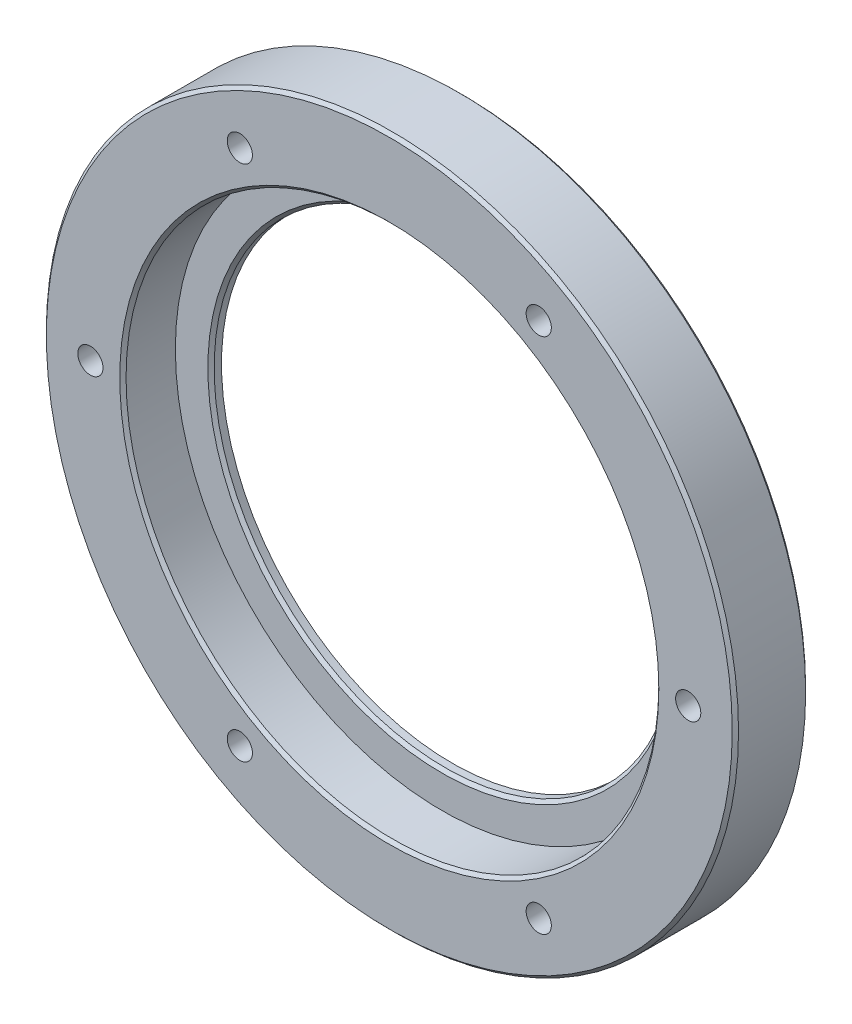
SolidWorks part; units mm, degrees
other "Markup1"
sketch "Sketch6" plane through (33, 33, 7.2446) normal (0.7002, 0.6134, 0.3652) x (0.5544, -0.7895, 0.2632)
material "6061-O (SS)"
ref_plane "Front Plane" through (0, 0, 0) normal (0, 0, 1) x (1, 0, 0)
ref_plane "Top Plane" through (0, 0, 0) normal (0, 1, 0) x (1, 0, 0)
ref_plane "Right Plane" through (0, 0, 0) normal (1, 0, 0) x (0, 0, -1)
sketch "Sketch1" plane through (0, 0, 0) normal (0, 0, 1) x (1, 0, 0)
  circle A0 centre (0, 0) radius 33
  dimension "D1" = 66
extrude "Main Body" add sketch "Sketch1" along normal blind 7
sketch "Sketch2" plane through (0, 0, 7) normal (0, 0, 1) x (1, 0, 0)
  circle A0 centre (0, 0) radius 22
  dimension "D1" = 44
extrude "Optical Cutout" cut sketch "Sketch2" against normal through all
sketch "Sketch3" plane through (0, 0, 7) normal (0, 0, 1) x (1, 0, 0)
  circle A0 centre (0, 0) radius 25.4
  dimension "D1" = 50.8
extrude "Window Cutout" cut sketch "Sketch3" against normal blind 5
sketch "Sketch4" plane through (0, 0, 0) normal (0, 0, -1) x (-1, 0, 0)
  line L1 (0, 0) -> (0, 33) construction
  line L2 (0, 0) -> (16.5, 28.5788) construction
  line L3 (0, 0) -> (14.25, 24.6817) construction
  circle A1 centre (0, 0) radius 33 construction
  circle A2 centre (14.25, 24.6817) radius 1.2
  point P4 (0, 0)
  dimension "D1" = 2.4
  dimension "D3" = 30
  dimension "D4" = 28.5
extrude "Cut-Extrude3" cut sketch "Sketch4" against normal through all
sketch "Sketch5" plane through (0, 0, 0) normal (0, 0, -1) x (-1, 0, 0)
  circle A1 centre (14.25, 24.6817) radius 2.1
  point P1 (0, 0)
  point P4 (14.25, 24.6817)
  dimension "D2" = 4.2
extrude "Cut-Extrude4" cut sketch "Sketch5" against normal blind 2
pattern_circular "Circular Pattern" count 6 over 360 about axis through (0, 0, 7) along (0, 0, -1) of "Cut-Extrude3", "Cut-Extrude4"
chamfer "Bubble Control Chamfer" distance 1 distance2 2 1 edges at (22, 0, 0) first distance on face at (22, 0, 0)
ref_axis "Central Axis" through (0, 0, 45.243) along (0, 0, -1)
chamfer "Chamfer1" distance 0.3 angle 45 4 edges at (33, 0, 0) (33, 0, 7) (25.4, 0, 7) (22, 0, 2)
